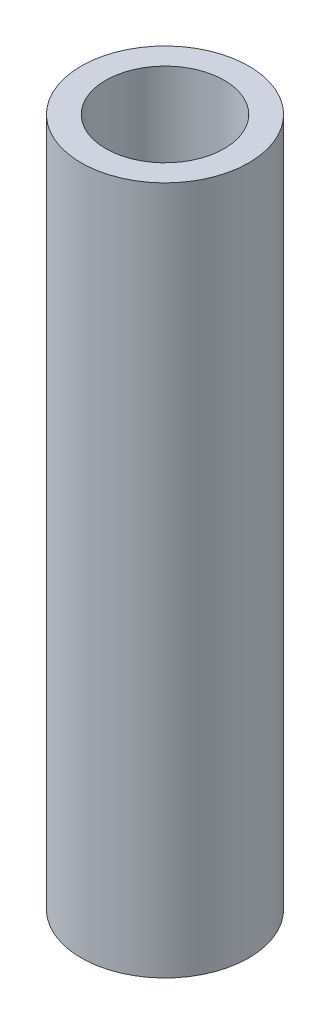
SolidWorks part; units mm, degrees
material "Rubber"
ref_plane "Front Plane" through (0, 0, 0) normal (0, 0, 1) x (1, 0, 0)
ref_plane "Top Plane" through (0, 0, 0) normal (0, 1, 0) x (1, 0, 0)
ref_plane "Right Plane" through (0, 0, 0) normal (1, 0, 0) x (0, 0, -1)
sketch "Sketch1" plane through (0, 0, 0) normal (0, 1, 0) x (1, 0, 0)
  circle A0 centre (0, 0) radius 6.025
extrude "Extrude-Thin1" add sketch "Sketch1" along normal blind 70 thin thin type one direction wall 2.5
